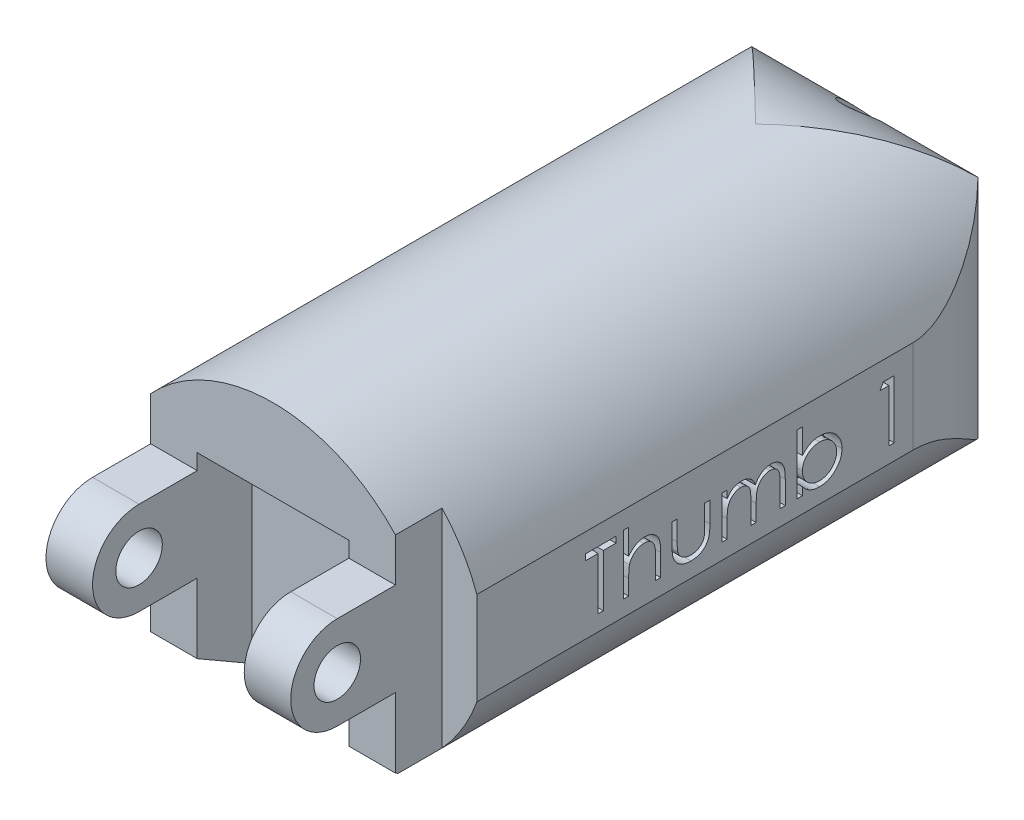
SolidWorks part; units mm, degrees
material "PET"
ref_plane "Front Plane" through (0, 0, 0) normal (0, 0, 1) x (1, 0, 0)
ref_plane "Top Plane" through (0, 0, 0) normal (0, 1, 0) x (1, 0, 0)
ref_plane "Right Plane" through (0, 0, 0) normal (1, 0, 0) x (0, 0, -1)
sketch "Sketch1" plane through (0, 0, 0) normal (0, 0, 1) x (1, 0, 0)
  line L0 (0, 0) -> (0, 5.08)
  line L3 (17.1704, 5.08) -> (17.1704, 0)
  arc A2 (0, 5.08) -> (17.1704, 5.08) centre (8.5852, 2.0064) cw
  arc A3 (0, 0) -> (17.1704, 0) centre (8.5852, 3.0736) ccw
  point P7 (8.5852, -6.0452)
  point P8 (8.5852, 11.1252)
  dimension "D1" = 17.1704
  dimension "D2" = 17.1704
  dimension "D3" = 5.08
extrude "Boss-Extrude1" add sketch "Sketch1" along normal mid plane 34.925 contours A2 L3 A3 L0
sketch "Sketch2" plane through (0, 0, 0) normal (1, 0, 0) x (0, 0, -1)
  line L4 (15.875, 2.54) -> (-49984.125, 2.54) construction
  line L5 (17.4625, 5.08) -> (17.4625, 0) construction
  line L6 (-17.4625, 5.08) -> (-17.4625, 0) construction
  line L7 (-17.4625, -6.0452) -> (-17.4625, -3.048)
  line L8 (-12.2712, -6.0452) -> (-17.4625, -6.0452)
  line L9 (-17.4625, -3.048) -> (-12.2712, -6.0452)
  line L10 (0, -1000) -> (0, 49000) construction
  line L30 (-17.4625, 0) -> (-17.4625, -6.0452) construction
  point P0 (-15.0884, 2.54)
  point P11 (17.4625, 2.54)
  point P14 (-17.4625, 2.54)
  dimension "D1" = 60
  dimension "D2" = 5.588
extrude "Cut-Extrude1" cut sketch "Sketch2" along normal through all
sketch "Sketch3" plane through (0, 0, 17.4625) normal (0, 0, 1) x (1, 0, 0)
  line L3 (-4.9679, 2.54) -> (22.8791, 2.54) construction
  line L4 (17.1704, 5.08) -> (17.1704, 0) construction
  line L9 (8.5852, -997.6135) -> (8.5852, 49002.3865) construction
  arc A0 (17.1704, 5.08) -> (0, 5.08) centre (8.5852, 2.0064) ccw construction
  arc A3 (17.1704, 5.08) -> (0, 5.08) centre (8.5852, 2.0064) ccw
  arc A5 (15.9747, 4.6519) -> (1.1957, 4.6519) centre (8.5852, 2.0064) ccw
  arc A6 (5.4277, 9.1921) -> (11.7427, 9.1921) centre (8.5852, 9.525) ccw
  arc A7 (15.9747, 0.4281) -> (1.1957, 0.4281) centre (8.5852, 3.0736) cw
  arc A8 (5.4277, -4.1121) -> (11.7427, -4.1121) centre (8.5852, -4.445) cw
  arc A9 (15.9747, 4.6519) -> (1.1957, 4.6519) centre (8.5852, 2.0064) ccw construction
  point P14 (8.5852, 6.35)
  point P25 (17.1704, 2.54)
  line M23 (1.8266, -3.048) -> (15.3438, -3.048)
  dimension "D2" = 1.27
  dimension "D4" = 3.175
  dimension "D5" = 3.81
extrude "Cut-Extrude2" cut sketch "Sketch3" against normal through all contours A8 A7 | A8 M23
ref_plane "Plane1" through (0, 0, 0) normal (0, 0, -1) x (-1, 0, 0)
ref_point "Point1"
ref_plane "Plane2" through (8.5852, 0, 0) normal (1, 0, 0) x (0, 0, -1)
sketch "Sketch4" plane through (0, 0, 0) normal (-1, 0, 0) x (0, 0, 1)
  line L0 (-17.4625, -6.0452) -> (12.2712, -6.0452) construction
  line L1 (-17.4625, 0) -> (-17.4625, -6.0452) construction
  line L2 (-17.4625, 5.08) -> (-17.4625, 0) construction
  line L3 (-17.4625, 11.1252) -> (-17.4625, 5.08) construction
  line L4 (17.4625, 11.1252) -> (-17.4625, 11.1252) construction
  line L5 (-17.4625, -6.0452) -> (12.2712, -6.0452)
  line L6 (-17.4625, 0) -> (-17.4625, -6.0452)
  line L7 (-17.4625, 5.08) -> (-17.4625, 0)
  line L8 (-17.4625, 11.1252) -> (-17.4625, 5.08)
  line L9 (17.4625, 11.1252) -> (-17.4625, 11.1252)
  arc A0 (-8.8773, 11.1252) -> (-8.8773, -6.0452) centre (-8.8773, 2.54) ccw
  point P9 (-17.4625, 2.54)
  point P10 (-17.4625, 2.54)
  line M1 (-17.4625, 0) -> (17.4625, 0)
  line M3 (17.4625, 5.08) -> (-17.4625, 5.08)
  line M4 (-17.4625, 5.08) -> (-17.4625, 0)
extrude "Cut-Extrude3" cut sketch "Sketch4" against normal through all contours A0 L9 L8 M3 | A0 M3 M4 | A0 L7 M1 | A0 L6 L5 M1
sketch "Sketch5" plane through (0, 0, 0) normal (0, 1, 0) x (1, 0, 0)
  line L0 (17.1704, 17.4625) -> (0, 17.4625) construction
  line L1 (17.1704, 17.0782) -> (17.1704, 17.4625) construction
  line L2 (17.1704, -17.4625) -> (17.1704, 17.0782) construction
  line L3 (0, -17.4625) -> (0, 17.0782) construction
  line L4 (17.1704, 17.4625) -> (0, 17.4625)
  line L5 (17.1704, 17.0782) -> (17.1704, 17.4625)
  line L6 (17.1704, -17.4625) -> (17.1704, 17.0782)
  line L7 (0, -17.4625) -> (0, 17.0782)
  line L8 (0, 17.0782) -> (0, 17.4625)
  arc A0 (0, 8.8773) -> (17.1704, 8.8773) centre (8.5852, 8.8773) cw
  point P9 (8.5852, 17.4625)
  point P10 (8.5852, 17.4625)
extrude "Cut-Extrude4" cut sketch "Sketch5" against normal through all both and the other way through all contours L4 A0 L6 L5 | L7 A0 L4 L8
ref_plane "Plane3" through (2.54, 0, 0) normal (1, 0, 0) x (0, 0, -1)
ref_plane "Plane4" through (14.6304, 0, 0) normal (1, 0, 0) x (0, 0, -1)
sketch "Sketch8" plane through (2.54, 0, 0) normal (1, 0, 0) x (0, 0, -1)
  line L0 (-17.4625, 5.842) -> (-20.6375, 5.842)
  line L1 (-17.4625, 5.08) -> (-17.4625, 0) construction
  line L2 (-17.4625, 5.842) -> (-17.4625, 0.762)
  line L3 (-17.4625, 0.762) -> (-20.6375, 0.762)
  line L4 (-17.4625, 5.08) -> (-17.4625, 0) construction
  line L5 (-17.4625, 0) -> (8.8773, 0) construction
  line L6 (-17.4625, 0.762) -> (-17.4625, 0) construction
  line L7 (-17.4625, 0) -> (-16.1427, 0) construction
  arc A0 (-20.6375, 5.842) -> (-20.6375, 0.762) centre (-20.6375, 3.302) ccw
  circle A1 centre (-20.6375, 3.302) radius 1.27
  dimension "D1" = 2.54
  dimension "D2" = 5.08
  dimension "D3" = 3.175
  dimension "D4" = 3.302
extrude "Boss-Extrude3" add sketch "Sketch8" along normal mid plane 1.27
ref_plane "Plane5" through (8.5852, 0, 0) normal (1, 0, 0) x (0, 0, -1)
sketch "Sketch10" plane through (1.905, 0, 0) normal (-1, 0, 0) x (0, 0, 1)
  line L3 (17.4625, 5.842) -> (17.4625, 0.762)
  line L4 (17.4625, 0.762) -> (20.6375, 0.762)
  line L5 (20.6375, 5.842) -> (17.4625, 5.842)
  line L6 (17.4625, 5.842) -> (17.4625, 0.762)
  line L7 (17.4625, 0.762) -> (20.6375, 0.762)
  line L8 (20.6375, 5.842) -> (17.4625, 5.842)
  circle A0 centre (20.6375, 3.302) radius 1.27 construction
  arc A1 (20.6375, 0.762) -> (20.6375, 5.842) centre (20.6375, 3.302) ccw
  arc A2 (20.6375, 0.762) -> (20.6375, 5.842) centre (20.6375, 3.302) ccw
  circle A3 centre (20.6375, 3.302) radius 1.27
  dimension "D1" = 0
extrude "Boss-Extrude4" add sketch "Sketch10" along normal blind 1.27
mirror "Mirror1" about plane through (8.5852, 0, 0) normal (1, 0, 0) of "Boss-Extrude4", "Boss-Extrude3"
sketch "Sketch11" plane through (0.635, 0, 0) normal (-1, 0, 0) x (0, 0, 1)
  line L3 (20.6375, 5.842) -> (17.4625, 5.842)
  line L4 (17.4625, 5.842) -> (17.4625, 0.762)
  line L5 (17.4625, 0.762) -> (20.6375, 0.762)
  line L6 (20.6375, 5.842) -> (17.4625, 5.842)
  line L7 (17.4625, 5.842) -> (17.4625, 0.762)
  line L8 (17.4625, 0.762) -> (20.6375, 0.762)
  circle A0 centre (20.6375, 3.302) radius 1.27 construction
  circle A1 centre (20.6375, 3.302) radius 1.27
  arc A3 (20.6375, 0.762) -> (20.6375, 5.842) centre (20.6375, 3.302) ccw
  arc A4 (20.6375, 0.762) -> (20.6375, 5.842) centre (20.6375, 3.302) ccw
  dimension "D1" = 0
extrude "Cut-Extrude6" cut sketch "Sketch11" against normal blind 1.27
sketch "Sketch12" plane through (3.175, 0, 0) normal (1, 0, 0) x (0, 0, -1)
  line L3 (-17.4625, 0.762) -> (-17.4625, 5.842)
  line L4 (-17.4625, 5.842) -> (-20.6375, 5.842)
  line L5 (-20.6375, 0.762) -> (-17.4625, 0.762)
  line L6 (-17.4625, 0.762) -> (-17.4625, 5.842)
  line L7 (-17.4625, 5.842) -> (-20.6375, 5.842)
  line L8 (-20.6375, 0.762) -> (-17.4625, 0.762)
  circle A0 centre (-20.6375, 3.302) radius 1.27 construction
  arc A1 (-20.6375, 5.842) -> (-20.6375, 0.762) centre (-20.6375, 3.302) ccw
  arc A2 (-20.6375, 5.842) -> (-20.6375, 0.762) centre (-20.6375, 3.302) ccw
  circle A3 centre (-20.6375, 3.302) radius 1.27
  dimension "D1" = 0
extrude "Boss-Extrude5" add sketch "Sketch12" along normal blind 1.27
mirror "Mirror2" about plane through (8.5852, 0, 0) normal (1, 0, 0) of "Cut-Extrude6", "Boss-Extrude5"
sketch "Sketch13" plane through (0, 0, 17.4625) normal (0, 0, 1) x (1, 0, 0)
  line L1 (0, -6.0452) -> (1.905, -6.0452)
  line L2 (0, -6.0452) -> (0, 8.2135)
  line L3 (0, 8.2135) -> (1.905, 8.2135)
  line L4 (1.905, -6.0452) -> (1.905, 8.2135)
  line L5 (8.5852, 0.762) -> (8.5852, 14.3113) construction
  line L6 (1.905, 5.842) -> (1.905, 0.762) construction
  line L7 (15.2654, -6.0452) -> (15.2654, 8.2135)
  line L8 (17.1704, 8.2135) -> (15.2654, 8.2135)
  line L9 (17.1704, -6.0452) -> (17.1704, 8.2135)
  line L10 (17.1704, -6.0452) -> (15.2654, -6.0452)
  line L11 (3.2723, -6.0452) -> (13.6472, -6.0452) construction
  line L12 (0, 0) -> (0, 5.08) construction
  line L14 (4.445, 0.762) -> (12.7254, 0.762) construction
  line L15 (12.7254, 0.762) -> (12.7254, 5.842) construction
  line L17 (4.445, 0.762) -> (4.445, 5.842) construction
  arc A0 (1.8266, -3.048) -> (15.3438, -3.048) centre (8.5852, 3.0736) ccw construction
  arc A1 (17.1704, 5.08) -> (0, 5.08) centre (8.5852, 2.0064) ccw construction
extrude "Cut-Extrude7" cut sketch "Sketch13" against normal blind 2.54
sketch "Sketch18" plane through (0, 0, 0) normal (0, 1, 0) x (1, 0, 0)
  circle A1 centre (8.5852, 14.5923) radius 0.9525
  arc A2 (14.7608, 14.8411) -> (8.5852, 17.4625) centre (8.5852, 8.8773) ccw construction
  dimension "D1" = 1.905
  dimension "D2" = 5.715
extrude "Cut-Extrude12" cut sketch "Sketch18" against normal through all both and the other way through all
sketch "Sketch19" plane through (0, 0, 17.4625) normal (0, 0, 1) x (1, 0, 0)
  line L0 (4.445, 0.762) -> (4.445, 5.842) construction
  line L1 (12.7254, 6.692) -> (4.445, 6.692)
  line L2 (12.7254, 6.692) -> (12.7254, -4.7752)
  line L3 (12.7254, -4.7752) -> (4.445, -4.7752)
  line L4 (4.445, 6.692) -> (4.445, -4.7752)
  line L5 (12.7254, 0.762) -> (12.7254, 5.842) construction
  line L6 (12.7254, 5.842) -> (15.2654, 5.842) construction
  arc A0 (5.4277, -4.1121) -> (11.7427, -4.1121) centre (8.5852, 3.0736) ccw construction
  dimension "D1" = 0.85
extrude "Cut-Extrude13" cut sketch "Sketch19" against normal up to vertex (2.9916 mm away)
sketch "Sketch20" plane through (0, 0, 14.4709) normal (0, 0, 1) x (1, 0, 0)
  line L1 (10.9262, 5.4737) -> (11.9422, 5.4737)
  line L3 (10.9262, 6.2357) -> (11.9422, 6.2357)
  line L5 (17.1704, 0) -> (17.1704, 5.08) construction
  line L7 (12.7254, 5.842) -> (15.2654, 5.842) construction
  arc A0 (11.9422, 6.2357) -> (11.9422, 5.4737) centre (11.9422, 5.8547) cw
  arc A1 (10.9262, 6.2357) -> (10.9262, 5.4737) centre (10.9262, 5.8547) ccw
  point P6 (10.5452, 5.8547)
  point P7 (12.3232, 5.8547)
  dimension "D1" = 0.381
  dimension "D2" = 1.778
  dimension "D3" = 4.8472
  dimension "D4" = 0.0127
extrude "Cut-Extrude14" cut sketch "Sketch20" against normal blind 16.51
sketch "Sketch21" plane through (17.1704, 0, 0) normal (1, 0, 0) x (0, 0, -1)
  text T0 "Thumb 1"
extrude "Cut-Extrude15" cut sketch "Sketch21" against normal blind 1
fillet "Fillet1" radius 1.27 1 edges at (8.7576, -1.2747, -15.5291)
equation "\"D1@Sketch1\"=0.676"
equation "\"D2@Sketch1\"=0.676"
equation "\"D1@Boss-Extrude1\"=1.375"
